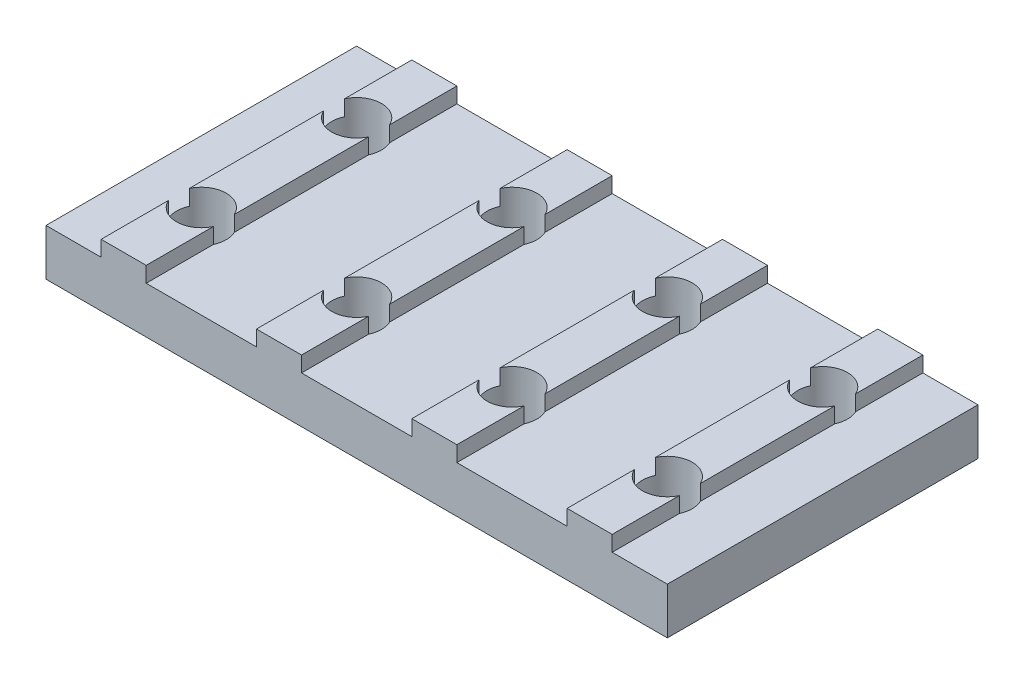
SolidWorks part; units mm, degrees
ref_plane "Front Plane" through (0, 0, 0) normal (0, 0, 1) x (1, 0, 0)
ref_plane "Top Plane" through (0, 0, 0) normal (0, 1, 0) x (1, 0, 0)
ref_plane "Right Plane" through (0, 0, 0) normal (1, 0, 0) x (0, 0, -1)
sketch "Esquisse1" plane through (0, 0, 0) normal (0, 0, 1) x (1, 0, 0)
  line L0 (-5, 0) -> (-5, 3)
  line L1 (-5, 3) -> (-1.45, 3)
  line L2 (-1.45, 3) -> (-1.45, 4)
  line L3 (-1.45, 4) -> (1.45, 4)
  line L4 (1.45, 4) -> (1.45, 3)
  line L5 (1.45, 3) -> (5, 3)
  line L6 (5, 3) -> (5, 0)
  line L7 (5, 0) -> (-5, 0)
  point P11 (0, 0)
  dimension "D1" = 10
  dimension "D2" = 3
  dimension "D3" = 1
  dimension "D4" = 2.9
  dimension "D5" = 3.55
extrude "Main" add sketch "Esquisse1" along normal blind 20
sketch "Esquisse2" plane through (0, 4, 0) normal (0, 1, 0) x (1, 0, 0)
  line L0 (0, -2.2) -> (0, 2.2) construction
  line L1 (-1.45, 0) -> (-5, 0) construction
  line L2 (-1.45, -20) -> (-5, -20) construction
  circle A0 centre (0, -5) radius 1.6
  circle A1 centre (0, -15) radius 1.6
  dimension "D2" = 5
  dimension "D3" = 3.2
  dimension "D1" = 5
extrude "TopHole" cut sketch "Esquisse2" against normal through all
ref_axis "Axe1" through (-5.5, 0, 0) along (1, 0, 0)
pattern_linear "Répétition linéaire1" count 4 spacing 10 along (-1, 0, 0) of "TopHole", "Main"
